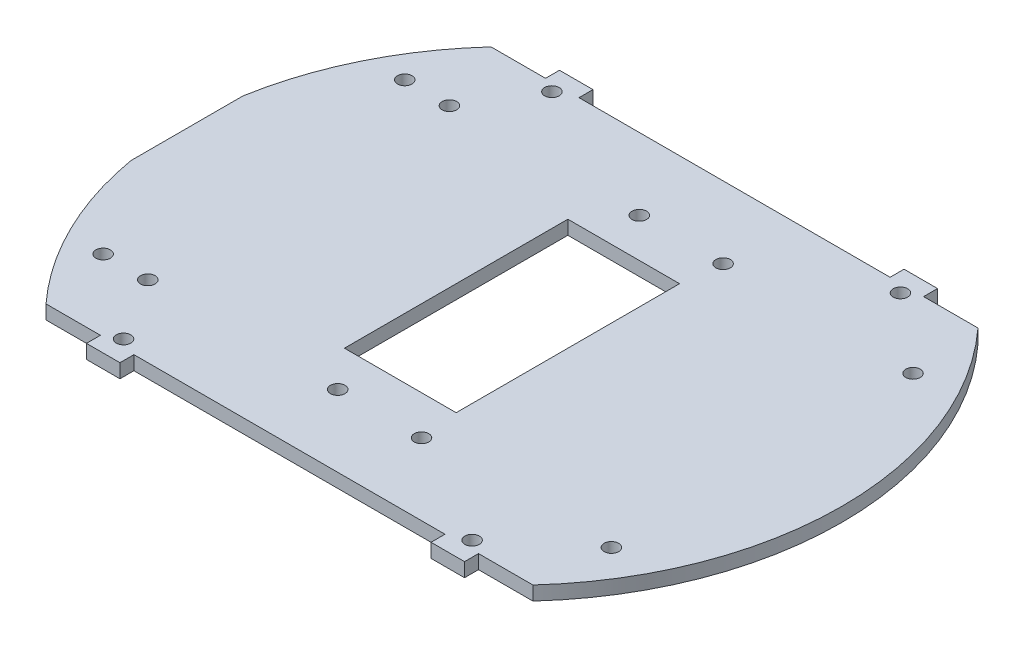
SolidWorks part; units mm, degrees
material "Acrylic (Medium-high impact)"
ref_plane "Front Plane" through (0, 0, 0) normal (0, 0, 1) x (1, 0, 0)
ref_plane "Top Plane" through (0, 0, 0) normal (0, 1, 0) x (1, 0, 0)
ref_plane "Right Plane" through (0, 0, 0) normal (1, 0, 0) x (0, 0, -1)
sketch "Sketch1" plane through (0, 0, 0) normal (0, 1, 0) x (1, 0, 0)
  line L0 (-73.9169, 12.7) -> (-73.9169, -12.7)
  line L1 (-35.3642, -50.6035) -> (-35.3642, -53.7785)
  line L2 (-55.356, -50.6035) -> (-42.9842, -50.6035)
  line L3 (-55.356, 50.6035) -> (-42.9842, 50.6035)
  line L4 (-48.5169, -34.29) -> (-48.5169, 34.29) construction
  line L5 (-48.5169, 34.29) -> (-5.3369, 34.29) construction
  line L6 (-5.3369, 34.29) -> (-5.3369, -34.29) construction
  line L7 (-5.3369, -34.29) -> (-48.5169, -34.29) construction
  line L8 (-73.9169, 0) -> (-48.5169, 0) construction
  line L9 (0, 50.6035) -> (0, -51.6195) construction
  line L10 (-73.9169, 12.7) -> (-73.9169, -12.7) construction
  line L11 (-12.7, 25.4) -> (12.7, 25.4)
  line L12 (-12.7, 25.4) -> (-12.7, -25.4)
  line L13 (-12.7, -25.4) -> (12.7, -25.4)
  line L14 (12.7, 25.4) -> (12.7, -25.4)
  line L15 (0, 0) -> (0, 25.4) construction
  line L16 (0, 0) -> (-12.7, 0) construction
  line L17 (13.7131, 34.29) -> (13.7131, -34.29) construction
  line L18 (13.7131, -34.29) -> (56.8931, -34.29) construction
  line L19 (56.8931, -34.29) -> (56.8931, 34.29) construction
  line L20 (56.8931, 34.29) -> (13.7131, 34.29) construction
  line L21 (39.6269, 48.6985) -> (39.6269, 50.6035) construction
  line L22 (39.6269, -48.6985) -> (39.6269, -50.6035) construction
  line L23 (-39.6269, -48.6985) -> (-39.6269, -50.6035) construction
  line L24 (-39.6269, 48.6985) -> (-39.6269, 50.6035) construction
  line L25 (39.6269, 48.6985) -> (41.2779, 48.6985) construction
  line L26 (39.6269, -48.6985) -> (41.2779, -48.6985) construction
  line L27 (-35.3642, -50.6035) -> (35.3642, -50.6035)
  line L28 (35.3642, -50.6035) -> (35.3642, -53.7785)
  line L29 (35.3642, -53.7785) -> (42.9842, -53.7785)
  line L30 (42.9842, -50.6035) -> (42.9842, -53.7785)
  line L31 (-35.3642, -53.7785) -> (-42.9842, -53.7785)
  line L32 (-42.9842, -50.6035) -> (-42.9842, -53.7785)
  line L33 (42.9842, 50.6035) -> (42.9842, 53.7785)
  line L34 (35.3642, 53.7785) -> (42.9842, 53.7785)
  line L35 (35.3642, 50.6035) -> (35.3642, 53.7785)
  line L36 (-35.3642, 50.6035) -> (-35.3642, 53.7785)
  line L37 (-35.3642, 53.7785) -> (-42.9842, 53.7785)
  line L38 (-42.9842, 50.6035) -> (-42.9842, 53.7785)
  line L39 (42.9842, -50.6035) -> (55.356, -50.6035)
  line L40 (42.9842, 50.6035) -> (55.356, 50.6035)
  line L41 (-35.3642, 50.6035) -> (35.3642, 50.6035)
  arc A0 (-73.9169, -12.7) -> (-55.356, -50.6035) centre (0, 0) ccw
  circle A1 centre (13.7131, 34.29) radius 1.651
  arc A2 (-55.356, 50.6035) -> (-73.9169, 12.7) centre (0, 0) ccw
  arc A3 (55.356, -50.6035) -> (55.356, 50.6035) centre (0, 0) ccw
  circle A4 centre (-58.6769, -34.29) radius 1.651
  circle A5 centre (-58.6769, 34.29) radius 1.651
  circle A6 centre (-39.6269, 48.6985) radius 1.651
  circle A7 centre (39.6269, 48.6985) radius 1.651
  circle A8 centre (-39.6269, -48.6985) radius 1.651
  circle A9 centre (39.6269, -48.6985) radius 1.651
  circle A10 centre (56.8931, 34.29) radius 1.651
  circle A11 centre (-58.6769, 34.29) radius 1.651 construction
  circle A12 centre (-48.5169, 34.29) radius 1.651
  circle A13 centre (-5.3369, 34.29) radius 1.651
  circle A14 centre (-5.3369, -34.29) radius 1.651
  circle A15 centre (-48.5169, -34.29) radius 1.651
  circle A16 centre (13.7131, -34.29) radius 1.651
  circle A17 centre (56.8931, -34.29) radius 1.651
  dimension "D3" = 3.302
  dimension "D1" = 43.18
  dimension "D2" = 68.58
  dimension "D4" = 25.4
  dimension "D5" = 25.4
  dimension "D6" = 50.8
  dimension "D7" = 19.05
  dimension "D10" = 19.05
extrude "Boss-Extrude1" add sketch "Sketch1" along normal blind 3.175
